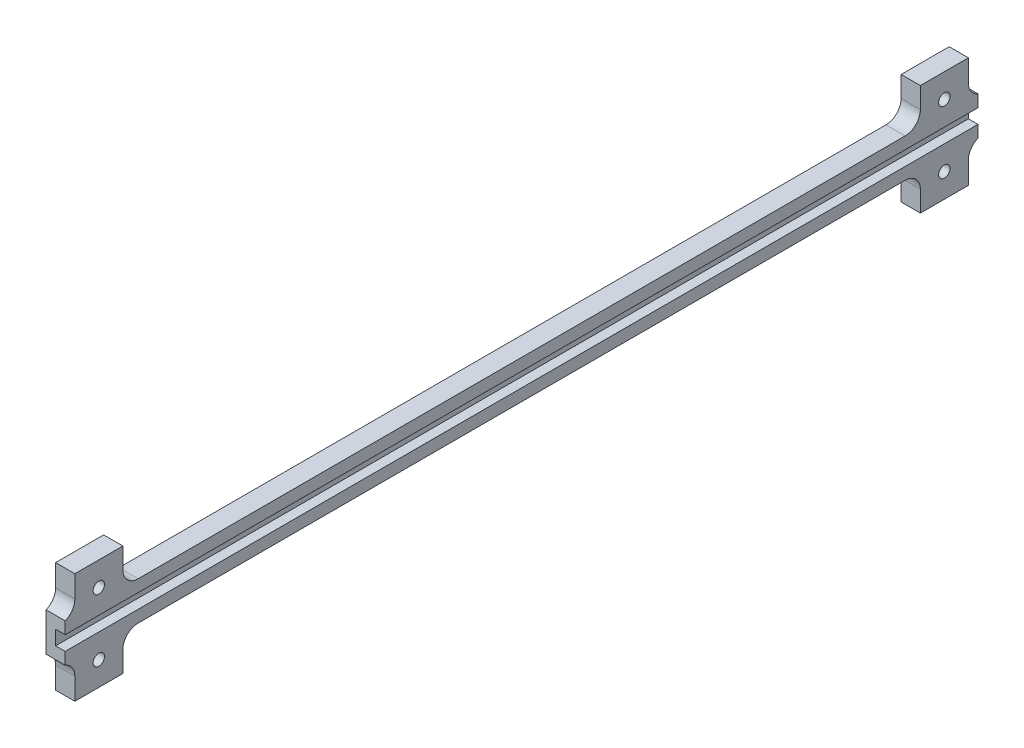
SolidWorks part; units mm, degrees
ref_plane "Front Plane" through (0, 0, 0) normal (0, 0, 1) x (1, 0, 0)
ref_plane "Top Plane" through (0, 0, 0) normal (0, 1, 0) x (1, 0, 0)
ref_plane "Right Plane" through (0, 0, 0) normal (1, 0, 0) x (0, 0, -1)
sketch "Sketch1" plane through (0, 0, 0) normal (0, 0, 1) x (1, 0, 0)
  line L0 (-1, 2) -> (-1, -2)
  line L1 (-1, -2) -> (1, -2)
  line L2 (1, -2) -> (1, -0.75)
  line L3 (1, -0.75) -> (0, -0.75)
  line L4 (0, -0.75) -> (0, 0.75)
  line L5 (0, 0.75) -> (1, 0.75)
  line L6 (1, 0.75) -> (1, 2)
  line L7 (1, 2) -> (-1, 2)
  dimension "D1" = 1
  dimension "D2" = 1
  dimension "D3" = 1.5
  dimension "D4" = 4
extrude "Boss-Extrude1" add sketch "Sketch1" along normal blind 95
sketch "Sketch4" plane through (1, 0, 0) normal (1, 0, 0) x (0, 0, -1)
  line L0 (-95, 0.75) -> (0, 0.75) construction
  line L1 (-89, 0.75) -> (-97.5, 0.75) construction
  line L2 (-89, 0.75) -> (-89, 5.75) construction
  line L3 (-89, 5.75) -> (-97.5, 5.75) construction
  line L4 (-97.5, 0.75) -> (-97.5, 5.75) construction
  line L5 (-95, -0.75) -> (0, -0.75) construction
  line L6 (-6, 0.75) -> (2.5, 0.75) construction
  line L7 (-6, 0.75) -> (-6, 5.75) construction
  line L8 (-6, 5.75) -> (2.5, 5.75) construction
  line L9 (2.5, 0.75) -> (2.5, 5.75) construction
  line L10 (-6, -0.75) -> (2.5, -0.75) construction
  line L11 (-6, -0.75) -> (-6, -5.75) construction
  line L12 (-6, -5.75) -> (2.5, -5.75) construction
  line L13 (2.5, -0.75) -> (2.5, -5.75) construction
  line L14 (-47.5, 2) -> (-47.5, -2) construction
  line L15 (-89, -0.75) -> (-97.5, -0.75) construction
  line L16 (-89, -0.75) -> (-89, -5.75) construction
  line L17 (-89, -5.75) -> (-97.5, -5.75) construction
  line L18 (-97.5, -0.75) -> (-97.5, -5.75) construction
  line L19 (-95, 2) -> (0, 2) construction
  line L20 (-95, -2) -> (0, -2) construction
  line L22 (-89, 5.75) -> (-94, 5.75)
  line L23 (-89, 5.75) -> (-89, 0.75)
  line L24 (-89, 0.75) -> (-94, 0.75)
  line L25 (-94, 5.75) -> (-94, 0.75)
  line L26 (-89, -0.75) -> (-94, -0.75)
  line L27 (-89, -0.75) -> (-89, -5.75)
  line L28 (-89, -5.75) -> (-94, -5.75)
  line L29 (-94, -0.75) -> (-94, -5.75)
  line L30 (-6, 5.75) -> (-1, 5.75)
  line L31 (-6, 5.75) -> (-6, 0.75)
  line L32 (-6, 0.75) -> (-1, 0.75)
  line L33 (-1, 5.75) -> (-1, 0.75)
  line L34 (-6, -0.75) -> (-1, -0.75)
  line L35 (-6, -0.75) -> (-6, -5.75)
  line L36 (-6, -5.75) -> (-1, -5.75)
  line L37 (-1, -0.75) -> (-1, -5.75)
  dimension "D1" = 100
  dimension "D2" = 8.5
  dimension "D3" = 5
  dimension "D4" = 5
extrude "Boss-Extrude4" add sketch "Sketch4" against normal up to surface (2 mm away) up to face at (-1, 0, 47.5)
fillet "Fillet1" radius 1.5875 8 edges at (0, -2, 89) (0, 2, 89) (0, 2, 6) (0, 2, 1) (0, -2, 1) (0, -2, 6) (0, -2, 94) (0, 2, 94)
hole_wizard "#0-80 Tapped Hole1" positions "Sketch6" profile "Sketch5" tap size "#0-80" standard "ANSI Inch"
sketch "Sketch6" plane through (1, 0, 0) normal (1, 0, 0) x (0, 0, -1)
  line L1 (-91.5, 3.25) -> (-3.5, 3.25) construction
  line L2 (-91.5, 3.25) -> (-91.5, -3.25) construction
  line L3 (-91.5, -3.25) -> (-3.5, -3.25) construction
  line L4 (-3.5, 3.25) -> (-3.5, -3.25) construction
  line L5 (-94, 5.75) -> (-94, 3.4748) construction
  line L6 (-89, 5.75) -> (-94, 5.75) construction
  line L7 (-94, -5.75) -> (-89, -5.75) construction
  line L8 (-1, 3.4748) -> (-1, 5.75) construction
  point P0 (-91.5, 3.25)
  point P7 (-3.5, -3.25)
  point P126 (-91.5, -3.25)
  point P127 (-3.5, 3.25)
  dimension "D1" = 2.5
  dimension "D2" = 2.5
  dimension "D3" = 2.5
  dimension "D4" = 2.5
sketch "Sketch5" plane through (1, 3.25, 91.5) normal (0, 1, 0) x (0, 0, -1)
  line L0 (0, 0) -> (0, 4.3584)
  line L1 (0, 4.3584) -> (0.5956, 4.0005)
  line L2 (0.5956, 4.0005) -> (0.5956, 0)
  line L5 (0.5956, 0) -> (0, 0)
  line L10 (0, 4.3584) -> (-0.5956, 4.0005) construction
  line L11 (0, -6.35) -> (0, 107.95) construction
  dimension "Tap Drill Dia." = 1.1913
  dimension "Tap Drill Depth" = 4.0005
  dimension "Drill Angle" = 118
cosmetic thread "Hole Thread1" parameters "D1"=2, "D2"=1.524
cosmetic thread "Hole Thread2" parameters "D1"=2, "D2"=1.524
cosmetic thread "Hole Thread3" parameters "D1"=2, "D2"=1.524
cosmetic thread "Hole Thread4" parameters "D1"=2, "D2"=1.524
